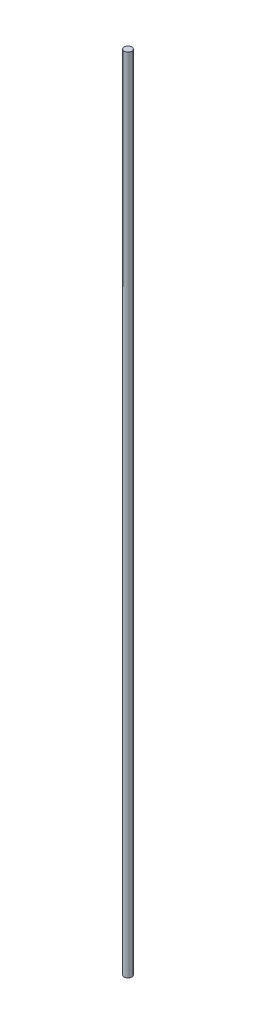
SolidWorks part; units mm, degrees
ref_plane "Спереди" through (0, 0, 0) normal (0, 0, 1) x (1, 0, 0)
ref_plane "Сверху" through (0, 0, 0) normal (0, 1, 0) x (1, 0, 0)
ref_plane "Справа" through (0, 0, 0) normal (1, 0, 0) x (0, 0, -1)
sketch "Эскиз2" plane through (0, 0, 0) normal (0, 0, 1) x (1, 0, 0)
  line L0 (0, 350.0223) -> (-5, 350.0223) construction
  line L5 (-2.5, 350.0223) -> (0, 350.0223)
  line L6 (-2.5, 350.0223) -> (-2.5, -179.3777)
  line L7 (-2.5, -179.3777) -> (0, -179.3777)
  line L8 (0, 350.0223) -> (0, -179.3777)
  line L9 (-2.5, 350.0223) -> (0, -179.3777) construction
  line L10 (-2.5, -179.3777) -> (0, 350.0223) construction
  line L13 (-25.8353, -179.3777) -> (28.1755, -179.3777) construction
  point P0 (-1.25, 85.3223)
  point P12 (0, 0)
  dimension "D1" = 2.5
revolve "Повернуть1" add sketch "Эскиз2" angle 360 about L6
equation "\"Ширина груза\"= 160"
equation "\"Глубина груза\"= 240"
equation "\"Высота груза\"= 160"
equation "\"Ширина ячейки\"= \"Ширина груза\" + 10"
equation "\"Глубина ячейки\"= \"Глубина груза\" + 10"
equation "\"Высота ячейки\"= \"Высота груза\" + 10 + 13"
equation "\"Колво ячеек ширина\"= 2"
equation "\"Колво ячеек высота\"= 2"
equation "\"Толщина стенки\"= \"Толщина тонких панелей\""
equation "\"Крепление дверцы\"= 5 "
equation "\"Ширина рейки\"= \"Толщина шестерни\""
equation "\"Высота рейки\"= 20"
equation "\"Высота пола\"= 2*\"Толщина тонких панелей\""
equation "\"Колво полозьев\"= 5"
equation "\"Отступ рейки\"= 20"
equation "\"Глубина каретки\"= \"Глубина ячейки\" + 30 + \"Мотор Y высота корпуса\" + 20"
equation "\"Длинна рейки\"= (\"Ширина ячейки\"+\"Толщина вертикальных стенок\"+\"Крепление дверцы\")*\"Колво ячеек ширина\"+\"Ширина ячейки выгрузки\"*\"Колво выгрузки\"+\"Толщина вертикальных стенок\"+2*\"Отступ крепления мотора фиксации\"-\"Крепление дверцы\"*\"Колво ячеек ширина\""
equation "\"Отступ шпильки\"= 26"
equation "\"Диаметр шпильки\"= 5"
equation "\"Длинна шпильки\"= (\"Высота ячейки\"+\"Толщина горизонтальных плит\"+\"Высота пола\")*\"Колво ячеек высота\"+2*(\"Толщина горизонтальных плит\"+\"Отступ рейки\")"
equation "\"D1@Эскиз2\"= \"Диаметр шпильки\" / 2"
equation "\"Ширина пластины\"= 50  "
equation "\"Высота зона выгрузки\"= \"Высота ячейки\" * 2 + \"Толщина стенки\" * 2"
equation "\"Колво выгрузки\"= 1"
equation "\"Отступ крепления мотора фиксации\"= (\"Ширина пластины\"+20-\"Толщина вертикальных стенок\")/2"
equation "\"Мотор X ширина корпуса\"= 42.3"
equation "\"Мотор X высота корпуса\"= 42.3"
equation "\"Мотор X длина корпуса\"= 40"
equation "\"Мотор X вылет вала\"= 19.8"
equation "\"Мотор Y ширина корпуса\"= 42.3"
equation "\"Мотор Y высота корпуса\"= 42.3"
equation "\"Мотор Y длина корпуса\"= 48"
equation "\"Мотор Y вылет вала\"= 30"
equation "\"Мотор Z ширина корпуса\"= 42"
equation "\"Мотор Z высота корпуса\"= 42"
equation "\"Мотор Z длина корпуса\"= 40"
equation "\"Мотор Z вылет вала\"= 23"
equation "\"Мотор диаметр вала ПРЕДВ\"= 5"
equation "\"Мотор шаг крепления ПРЕДВ\"= 31"
equation "\"Мотор диаметр отверстий ПРЕДВ\"= 3"
equation "\"Мотор глубина отверстий ПРЕДВ\"= 4.5"
equation "\"Мотор диаметр буртика ПРЕДВ\"= 22"
equation "\"Мотор высота буртика ПРЕДВ\"= 2"
equation "\"Мотор диаметр шкива ПРЕДВ\"= 16"
equation "\"Мотор длина шкива ПРЕДВ\"= 12"
equation "\"Мотор отступ шкива ПРЕДВ\"= 5"
equation "\"Мотор X шаг градусов\"= 1.8"
equation "\"Мотор X ток А\"= 1.5"
equation "\"Мотор X сопротивление Ом\"= 1.3"
equation "\"Мотор X индуктивность мГн\"= 2"
equation "\"Мотор Y шаг градусов\"= 1.8"
equation "\"Мотор Y ток А\"= 2.2"
equation "\"Мотор Y сопротивление Ом\"= 0.9"
equation "\"Мотор Y индуктивность мГн\"= 2"
equation "\"Мотор Z шаг градусов\"= 1.8"
equation "\"Мотор Z ток А\"= 1"
equation "\"Мотор Z сопротивление Ом\"= 4"
equation "\"Мотор Z индуктивность мГн\"= 8"
equation "\"Мотор Y диаметр ротора\"= 25.78"
equation "\"Ширина ячейки выгрузки\"= \"Ширина ячейки\"+\"Толщина вертикальных стенок\"+2*\"Отступ крепления мотора фиксации\""
equation "\"Толщина тонких панелей\"= 6"
equation "\"Толщина вертикальных стенок\"= 6"
equation "\"Толщина горизонтальных плит\"= 6"
equation "\"Базовая высота корпуса\"= (\"Высота ячейки\"+\"Толщина тонких панелей\"+\"Высота пола\")*\"Колво ячеек высота\"+6*\"Толщина тонких панелей\"+\"Мотор X ширина корпуса\"+\"Мотор Y ширина корпуса\"+75"
equation "\"Высота корпуса\"= (\"Высота ячейки\"+\"Толщина горизонтальных плит\"+\"Высота пола\")*\"Колво ячеек высота\"+2*\"Толщина горизонтальных плит\"+4*\"Толщина тонких панелей\"+\"Мотор X ширина корпуса\"+\"Мотор Y ширина корпуса\"+75"
equation "\"Смещение центра корпуса\"= (\"Высота корпуса\"-\"Базовая высота корпуса\")/2-(\"Толщина горизонтальных плит\"-\"Толщина тонких панелей\")"
equation "\"Отметка пола\"= -\"Базовая высота корпуса\"/2+\"Толщина тонких панелей\""
equation "\"Отметка потолка\"= \"Отметка пола\"+\"Высота корпуса\"-2*\"Толщина горизонтальных плит\""
equation "\"Отметка верхней полки\"= \"Отметка потолка\"-(28+\"Толщина тонких панелей\")-\"Высота ячейки\"-\"Высота пола\""
equation "\"Отметка нижней полки\"= \"Отметка верхней полки\"-\"Высота ячейки\"-\"Высота пола\"-\"Толщина горизонтальных плит\""
equation "\"Толщина шестерни\"= 10"
